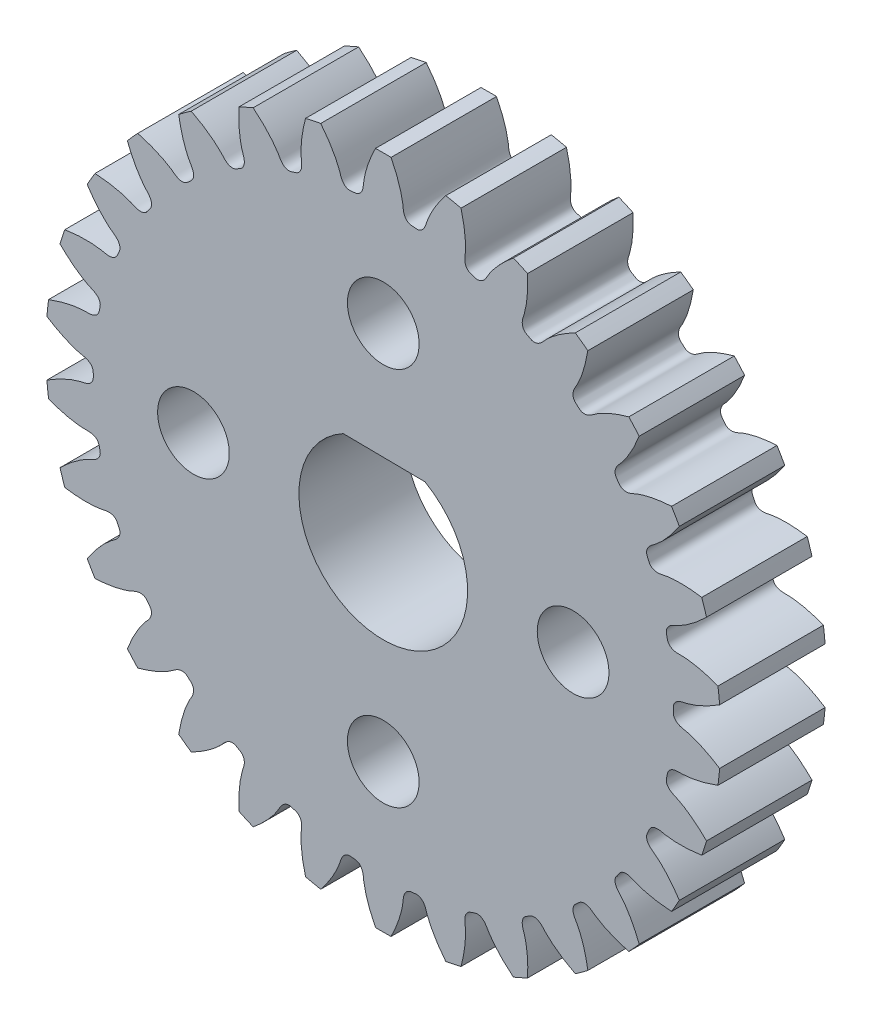
SolidWorks part; units mm, degrees
ref_plane "Front Plane" through (0, 0, 0) normal (0, 0, 1) x (1, 0, 0)
ref_plane "Top Plane" through (0, 0, 0) normal (0, 1, 0) x (1, 0, 0)
ref_plane "Right Plane" through (0, 0, 0) normal (1, 0, 0) x (0, 0, -1)
ref_axis "Axis1" through (0, 0, 55) along (0, 0, -1)
sketch "SketchRevolveSpurAssem30-42M1Pinion" plane through (0, 0, 0) normal (1, 0, 0) x (0, 0, -1)
  line L0 (0, 0) -> (1, 0) construction
  line L1 (-2.5, 0) -> (-2.5, 16)
  line L2 (-2.5, 16) -> (2.5, 16)
  line L3 (2.5, 16) -> (2.5, 0)
  line L4 (2.5, 0) -> (-2.5, 0)
  dimension "Side1" = 2.5
  dimension "OutsideRadius" = 16
  dimension "Side2" = 2.5
revolve "SpurAssem30-42M1Pinion" add sketch "SketchRevolveSpurAssem30-42M1Pinion" angle 360 about L0
sketch "SketchToothSpurAssem30-42M1Pinion" plane through (0, 0, 0) normal (0, 0, 1) x (1, 0, 0)
  arc A0 (15.9943, 1.3364) -> (15.9943, -1.3364) centre (0, 0) cw
  spline S0 degree 3 poles (15.9943, -1.3364) (15.8837, -1.2637) (15.7194, -1.1615) (15.501, -1.0381) (15.3487, -0.9574) (15.2035, -0.8855) (15.0659, -0.8219) (14.9363, -0.7663) (14.8149, -0.718) (14.702, -0.6767) (14.598, -0.6417) (14.503, -0.6127) (14.4174, -0.5891) (14.3024, -0.5601) (14.2046, -0.5444) (14.1253, -0.5225) (14.0977, -0.5139) (14.0706, -0.5045) (14.0441, -0.4943) (14.0179, -0.483) (13.9921, -0.4705) (13.9665, -0.4567) (13.941, -0.4412) (13.9157, -0.4237) (13.8904, -0.4038) (13.8653, -0.3809) (13.8406, -0.3545) (13.8168, -0.3239) (13.7946, -0.2885) (13.7753, -0.248) (13.7603, -0.2026) (13.7516, -0.1561) (13.748, -0.0881) (13.7514, 0) (13.748, 0.0881) (13.7516, 0.1561) (13.7603, 0.2026) (13.7753, 0.248) (13.7946, 0.2885) (13.8168, 0.3239) (13.8406, 0.3545) (13.8653, 0.3809) (13.8904, 0.4038) (13.9157, 0.4237) (13.941, 0.4412) (13.9665, 0.4567) (13.9921, 0.4705) (14.0179, 0.483) (14.0441, 0.4943) (14.0706, 0.5045) (14.0977, 0.5139) (14.1253, 0.5225) (14.2046, 0.5444) (14.3024, 0.5601) (14.4174, 0.5891) (14.503, 0.6127) (14.598, 0.6417) (14.702, 0.6767) (14.8149, 0.718) (14.9363, 0.7663) (15.0659, 0.8219) (15.2035, 0.8855) (15.3487, 0.9574) (15.501, 1.0381) (15.7194, 1.1615) (15.8837, 1.2637) (15.9943, 1.3364) knots 0 0 0 0 0.071866 0.104962 0.136167 0.16548 0.192903 0.218434 0.242074 0.263823 0.28368 0.301647 0.317722 0.331906 0.366034 0.371334 0.376561 0.381734 0.386878 0.392021 0.397196 0.402444 0.407814 0.413362 0.419154 0.425266 0.431778 0.438769 0.446303 0.454412 0.463067 0.472164 0.480031 0.5 0.519969 0.527836 0.536933 0.545588 0.553697 0.561231 0.568222 0.574734 0.580846 0.586638 0.592186 0.597556 0.602804 0.607979 0.613122 0.618266 0.623439 0.628666 0.633966 0.668094 0.682278 0.698353 0.71632 0.736177 0.757926 0.781566 0.807097 0.83452 0.863833 0.895038 0.928134 1 1 1 1
extrude "ToothExtrudeCutSpurAssem30-42M1Pinion" cut sketch "SketchToothSpurAssem30-42M1Pinion" against normal blind 2.5 and the other way blind 2.5
pattern_circular "PatternSpurAssem30-42M1Pinion" count 30 every 12 about axis through (0, 0, 55) along (0, 0, -1) of "ToothExtrudeCutSpurAssem30-42M1Pinion"
sketch "BoreRevolveSketch" plane through (0, 0, 0) normal (1, 0, 0) x (0, 0, -1)
  line L0 (0, 0) -> (1, 0) construction
  line L1 (-2.5, 0) -> (2.5, 0)
  line L2 (2.5, 0) -> (2.5, 2.5)
  line L3 (2.5, 2.5) -> (-2.5, 2.5)
  line L4 (-2.5, 2.5) -> (-2.5, 0)
  dimension "BoreSide1" = 2.5
  dimension "TaperSide1" = 2.5
  dimension "BoreSide2" = 2.5
  dimension "TaperSide2" = 2.5
revolve "BoreRevolveCut" cut sketch "BoreRevolveSketch" angle 360 about L0
sketch "AuxiliarySketchSpurAssem30-42M1Pinion" plane through (0, 0, 0) normal (0, 0, 1) x (1, 0, 0)
  circle A0 centre (0, 0) radius 15 construction
  circle A1 centre (0, 0) radius 14.0954 construction
  circle A2 centre (0, 0) radius 14.2441 construction
  circle A3 centre (0, 0) radius 16 construction
  circle A4 centre (0, 0) radius 13.75 construction
  dimension "PitchDiameter" = 30
  dimension "BaseDiameter" = 28.1908
  dimension "FormDiameter" = 28.4881
  dimension "MajorDiameter" = 32
  dimension "MinorDiameter" = 27.5
sketch "Sketch5" plane through (0, 0, 2.5) normal (0, 0, 1) x (1, 0, 0)
  line L0 (-1.8968, 3.5216) -> (1.9759, 3.4779)
  arc A0 (-1.8968, 3.5216) -> (1.9759, 3.4779) centre (0, 0) ccw
ref_plane "Plane1" through (12.1338, 10.4293, -2.5) normal (0, 0, 1) x (1, 0, 0)
extrude "Cut-Extrude2" cut sketch "Sketch5" against normal blind 10 contours L0 A0
sketch "Sketch6" plane through (0, 0, -2.5) normal (0, 0, -1) x (-1, 0, 0)
  circle A3 centre (-9, 0) radius 1.6
  circle A4 centre (0, 0) radius 9 construction
  circle A5 centre (0, 9) radius 1.6
  circle A6 centre (9, 0) radius 1.6
  circle A7 centre (0, -9) radius 1.6
  point P14 (0, 0)
  dimension "D1" = 4
  dimension "D2" = 18
extrude "Cut-Extrude3" cut sketch "Sketch6" against normal blind 3
hole_wizard "CSK for M3 Hex Socket Countersunk Head Screw2" positions "Sketch9" profile "Sketch10" countersink size "M3" standard "DIN" end condition through all
sketch "Sketch9" plane through (0, 0, -2.5) normal (0, 0, -1) x (-1, 0, 0)
  point P0 (0, 9)
  point P3 (-9, 0)
  point P6 (0, -9)
  point P9 (9, 0)
sketch "Sketch10" plane through (0, 9, -2.5) normal (1, 0, 0) x (0, 1, 0)
  line L0 (0, 0) -> (0, 5)
  line L1 (0, 5) -> (1.7, 5)
  line L2 (1.7, 5) -> (1.7, 1.77)
  line L3 (1.7, 1.77) -> (3.47, 0)
  line L5 (3.47, 0) -> (0, 0)
  line L6 (-1.7, 1.77) -> (-3.47, 0) construction
  line L11 (0, -6.35) -> (0, 107.95) construction
  dimension "Thru Hole Dia." = 3.4
  dimension "Thru Hole Depth" = 5
  dimension "Near C'Sink Dia." = 6.94
  dimension "Near C'Sink Angle" = 90
